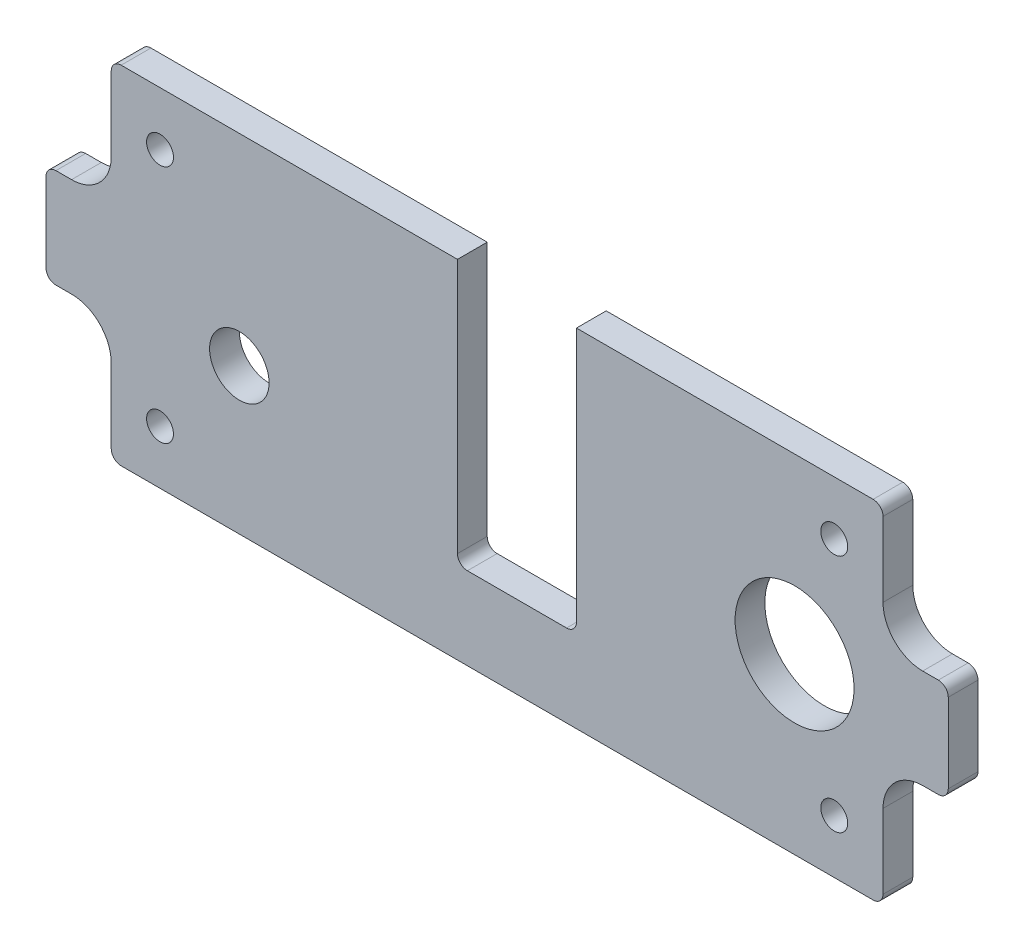
SolidWorks part; units mm, degrees
ref_plane "Front Plane" through (0, 0, 0) normal (0, 0, 1) x (1, 0, 0)
ref_plane "Top Plane" through (0, 0, 0) normal (0, 1, 0) x (1, 0, 0)
ref_plane "Right Plane" through (0, 0, 0) normal (1, 0, 0) x (0, 0, -1)
sketch "Sketch1" plane through (0, 0, 0) normal (0, 0, 1) x (1, 0, 0)
  line L16 (85.725, 56.3562) -> (85.725, 13.97)
  line L17 (85.725, 13.97) -> (66.675, 13.97)
  line L18 (66.675, 13.97) -> (66.675, 56.3562)
  line L19 (66.675, 56.3562) -> (11.2395, 56.3562)
  line L20 (11.2395, 56.3562) -> (11.2395, 42.8625)
  line L21 (4.8895, 36.5125) -> (0.7938, 36.5125)
  line L22 (0.7938, 36.5125) -> (0.7938, 20.6375)
  line L23 (0.7938, 20.6375) -> (4.8895, 20.6375)
  line L24 (11.2395, 14.2875) -> (11.2395, 0.7938)
  line L25 (11.2395, 0.7938) -> (134.8105, 0.7938)
  line L26 (134.8105, 0.7938) -> (134.8105, 14.2875)
  line L27 (141.1605, 20.6375) -> (145.2563, 20.6375)
  line L28 (145.2563, 20.6375) -> (145.2563, 36.5125)
  line L29 (145.2563, 36.5125) -> (141.1605, 36.5125)
  line L30 (134.8105, 42.8625) -> (134.8105, 56.3562)
  line L31 (134.8105, 56.3562) -> (85.725, 56.3562)
  line L32 (85.725, 56.3562) -> (85.725, 13.97)
  line L33 (85.725, 13.97) -> (66.675, 13.97)
  line L34 (66.675, 13.97) -> (66.675, 56.3562)
  line L35 (66.675, 56.3562) -> (11.2395, 56.3562)
  line L36 (11.2395, 56.3562) -> (11.2395, 42.8625)
  line L37 (4.8895, 36.5125) -> (0.7938, 36.5125)
  line L38 (0.7938, 36.5125) -> (0.7938, 20.6375)
  line L39 (0.7938, 20.6375) -> (4.8895, 20.6375)
  line L40 (11.2395, 14.2875) -> (11.2395, 0.7938)
  line L41 (11.2395, 0.7938) -> (134.8105, 0.7938)
  line L42 (134.8105, 0.7938) -> (134.8105, 14.2875)
  line L43 (141.1605, 20.6375) -> (145.2563, 20.6375)
  line L44 (145.2563, 20.6375) -> (145.2563, 36.5125)
  line L45 (145.2563, 36.5125) -> (141.1605, 36.5125)
  line L46 (134.8105, 42.8625) -> (134.8105, 56.3562)
  line L47 (134.8105, 56.3562) -> (85.725, 56.3562)
  arc A4 (4.8895, 36.5125) -> (11.2395, 42.8625) centre (4.8895, 42.8625) ccw
  arc A5 (11.2395, 14.2875) -> (4.8895, 20.6375) centre (4.8895, 14.2875) ccw
  arc A6 (141.1605, 20.6375) -> (134.8105, 14.2875) centre (141.1605, 14.2875) ccw
  arc A7 (134.8105, 42.8625) -> (141.1605, 36.5125) centre (141.1605, 42.8625) ccw
  arc A8 (4.8895, 36.5125) -> (11.2395, 42.8625) centre (4.8895, 42.8625) ccw
  arc A9 (11.2395, 14.2875) -> (4.8895, 20.6375) centre (4.8895, 14.2875) ccw
  arc A10 (141.1605, 20.6375) -> (134.8105, 14.2875) centre (141.1605, 14.2875) ccw
  arc A11 (134.8105, 42.8625) -> (141.1605, 36.5125) centre (141.1605, 42.8625) ccw
  dimension "D1" = 0
extrude "Boss-Extrude1" add sketch "Sketch1" along normal blind 4.7625
hole_wizard "3/8 (0.375) Diameter Hole1" positions "Sketch3" profile "Sketch2" hole size "3/8" standard "ANSI Inch" end condition through all
sketch "Sketch3" plane through (0, 0, 4.7625) normal (0, 0, 1) x (1, 0, 0)
  point P2 (31.75, 24.13)
sketch "Sketch2" plane through (31.75, 24.13, 4.7625) normal (1, 0, 0) x (0, -1, 0)
  line L0 (0, 0) -> (0, 4.7625)
  line L1 (0, 4.7625) -> (4.7625, 4.7625)
  line L2 (4.7625, 4.7625) -> (4.7625, 0)
  line L5 (4.7625, 0) -> (0, 0)
  line L11 (0, -6.35) -> (0, 107.95) construction
  dimension "Thru Hole Dia." = 9.525
  dimension "Thru Hole Depth" = 4.7625
hole_wizard "3/4 (0.75) Diameter Hole1" positions "Sketch5" profile "Sketch4" hole size "3/4" standard "ANSI Inch" end condition through all
sketch "Sketch5" plane through (0, 0, 4.7625) normal (0, 0, 1) x (1, 0, 0)
  point P0 (76.2, 28.575)
  point P3 (120.65, 28.575)
sketch "Sketch4" plane through (76.2, 28.575, 4.7625) normal (1, 0, 0) x (0, -1, 0)
  line L0 (0, 0) -> (0, 4.7625)
  line L1 (0, 4.7625) -> (9.525, 4.7625)
  line L2 (9.525, 4.7625) -> (9.525, 0)
  line L5 (9.525, 0) -> (0, 0)
  line L11 (0, -6.35) -> (0, 107.95) construction
  dimension "Thru Hole Dia." = 19.05
  dimension "Thru Hole Depth" = 4.7625
hole_wizard "#6 Clearance Hole1" positions "Sketch7" profile "Sketch6" hole size "#6" standard "ANSI Inch" end condition through all
sketch "Sketch7" plane through (0, 0, 4.7625) normal (0, 0, 1) x (1, 0, 0)
  point P0 (19.05, 9.398)
  point P3 (19.05, 47.752)
  point P6 (127, 47.752)
  point P9 (127, 9.398)
sketch "Sketch6" plane through (19.05, 9.398, 4.7625) normal (1, 0, 0) x (0, -1, 0)
  line L0 (0, 0) -> (0, 4.7625)
  line L1 (0, 4.7625) -> (2.1526, 4.7625)
  line L2 (2.1526, 4.7625) -> (2.1526, 0)
  line L5 (2.1526, 0) -> (0, 0)
  line L11 (0, -6.35) -> (0, 107.95) construction
  dimension "Thru Hole Dia." = 4.3053
  dimension "Thru Hole Depth" = 4.7625
fillet "Fillet1" radius 1.5875 10 edges at (66.675, 13.97, 2.3813) (85.725, 13.97, 2.3813) (134.8105, 56.3562, 2.3813) (145.2563, 36.5125, 2.3813) (145.2563, 20.6375, 2.3813) (134.8105, 0.7938, 2.3813) (11.2395, 56.3562, 2.3813) (0.7938, 36.5125, 2.3813) (0.7938, 20.6375, 2.3813) (11.2395, 0.7938, 2.3813)
